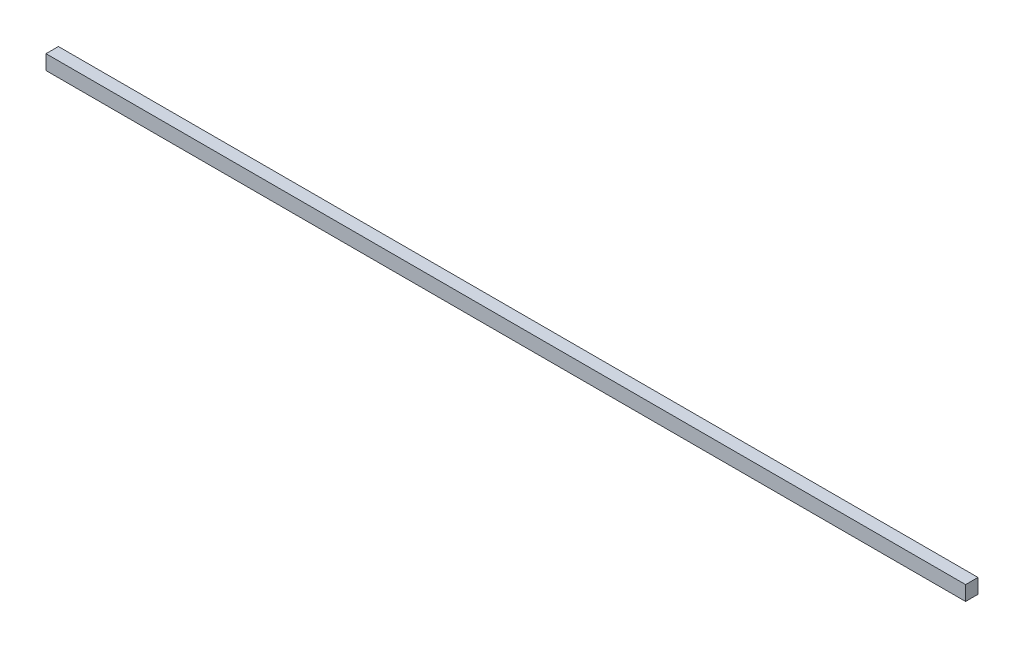
SolidWorks part; units mm, degrees
ref_plane "Спереди" through (0, 0, 0) normal (0, 0, 1) x (1, 0, 0)
ref_plane "Сверху" through (0, 0, 0) normal (0, 1, 0) x (1, 0, 0)
ref_plane "Справа" through (0, 0, 0) normal (1, 0, 0) x (0, 0, -1)
sketch "Эскиз1" plane through (0, 0, 0) normal (0, 0, 1) x (1, 0, 0)
  line L1 (-155.0828, 36.4367) -> (585.826, 36.4367)
  line L2 (-155.0828, 36.4367) -> (-155.0828, 48.2396)
  line L3 (-155.0828, 48.2396) -> (585.826, 48.2396)
  line L4 (585.826, 36.4367) -> (585.826, 48.2396)
extrude "Бобышка-Вытянуть1" add sketch "Эскиз1" along normal blind 10
